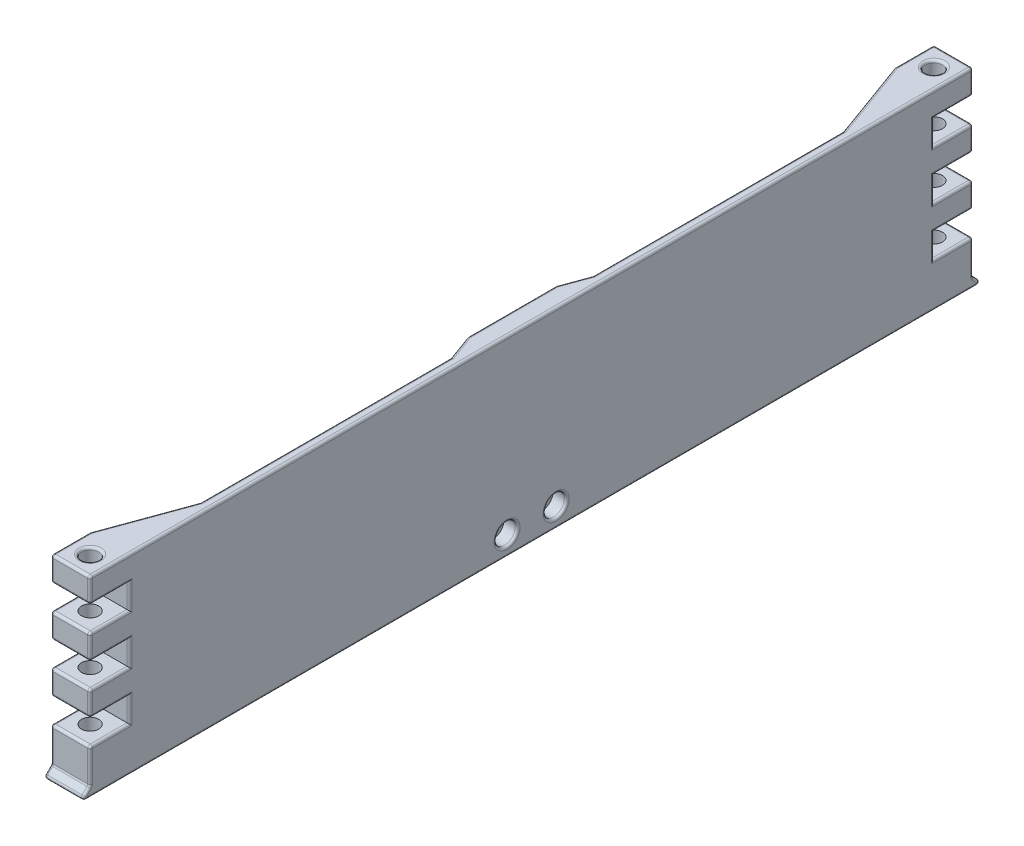
SolidWorks part; units mm, degrees
ref_plane "Front Plane" through (0, 0, 0) normal (0, 0, 1) x (1, 0, 0)
ref_plane "Top Plane" through (0, 0, 0) normal (0, 1, 0) x (1, 0, 0)
ref_plane "Right Plane" through (0, 0, 0) normal (1, 0, 0) x (0, 0, -1)
sketch "Sketch1" plane through (0, 0, 0) normal (1, 0, 0) x (0, 0, -1)
  line L1 (-45, -19.5) -> (45, -19.5)
  line L2 (-45, -5.5) -> (-45, -0.5)
  line L3 (-37, 19.5) -> (45, 19.5)
  line L4 (45, -19.5) -> (45, 19.5)
  line L5 (-45, -19.5) -> (45, 19.5) construction
  line L6 (-45, 19.5) -> (45, -19.5) construction
  line L8 (-47, -19.5) -> (-45, -19.5)
  line L12 (-37, 19.5) -> (-37, 14.5) construction
  line L13 (-37, 14.5) -> (-45, 14.5)
  line L14 (-37, 14.5) -> (-37, 9.5)
  line L15 (-37, 9.5) -> (-45, 9.5)
  line L16 (-37, 9.5) -> (-37, 4.5) construction
  line L17 (-37, 4.5) -> (-37, -0.5)
  line L18 (-37, -0.5) -> (-37, -5.5) construction
  line L19 (-37, -5.5) -> (-37, -10.5)
  line L20 (-37, 19.5) -> (-45, 19.5)
  line L21 (-45, 14.5) -> (-45, 19.5)
  line L22 (-37, -10.5) -> (-45, -10.5)
  line L23 (-37, -5.5) -> (-45, -5.5)
  line L24 (-37, -0.5) -> (-45, -0.5)
  line L25 (-37, 4.5) -> (-45, 4.5)
  line L26 (-45, 4.5) -> (-45, 9.5)
  line L43 (-45, -17.5) -> (-45, -10.5)
  line L44 (-45, -17.5) -> (-47, -19.5)
  line L45 (40, -19.5) -> (40, -15.5) construction
  line L46 (40, -15.5) -> (45, -15.5) construction
  circle A0 centre (40, -15.5) radius 2.15
  point P0 (0, 0)
  dimension "D9" = 4.3
  dimension "D1" = 39
  dimension "D2" = 90
  dimension "D3" = 2
  dimension "D4" = 8
  dimension "D5" = 5
  dimension "D6" = 2
  dimension "D7" = 4
  dimension "D8" = 5
extrude "Boss-Extrude1" add sketch "Sketch1" along normal blind 8 contours L13 L12 L3 L2 region at (0, -0.0156, -1.2577)
extrude "Boss-Extrude2" add sketch "Sketch1<3>" along normal blind 5.2 contours A0
sketch "Sketch1<3>" plane through (0, 0, 0) normal (1, 0, 0) x (0, 0, -1) same geometry as "Sketch1"
sketch "Sketch7" plane through (0, -19.5, 0) normal (0, -1, 0) x (1, 0, 0)
  line L1 (0, 47) -> (0, -45) construction
  line L2 (4, 41) -> (4, 45) construction
  line L4 (8, 37) -> (0, 37) construction
  line L5 (0, 37) -> (0, 45) construction
  line L6 (4, 45) -> (4, 47) construction
  line L7 (4, 45) -> (7, 45) construction
  line L8 (8, 37) -> (0, 45) construction
  line L9 (8, 47) -> (0, 47) construction
  line L10 (1.175, 39.369) -> (4, 37.738)
  line L11 (4, 37.738) -> (6.825, 39.369)
  line L12 (6.825, 39.369) -> (6.825, 42.631)
  line L13 (6.825, 42.631) -> (4, 44.262)
  line L14 (4, 44.262) -> (1.175, 42.631)
  line L15 (1.175, 42.631) -> (1.175, 39.369)
  line L16 (4, 37.738) -> (4, 37) construction
  line L17 (0, 45) -> (8, 45)
  line L18 (8, 47) -> (8, -45) construction
  line L19 (0, 45) -> (0, 47)
  circle A0 centre (4, 41) radius 1.75
  circle A1 centre (4, 41) radius 2.825 construction
  point P1 (0, 0)
  point P26 (4, 41)
  dimension "D4" = 5.65
  dimension "D5" = 3.5
  dimension "D1" = 2
  dimension "D3" = 8
  dimension "D6" = 2
extrude "Cut-Extrude3" cut sketch "Sketch7" against normal through all both and the other way through all contours A0 region at (4, -19.5, 41)
extrude "Cut-Extrude4" cut sketch "Sketch7<3>" against normal blind 6 and the other way through all contours L14 L15 L10 L11 L12 L13 A0 region at (1.2613, -19.5, 41)
sketch "Sketch7<3>" plane through (0, -19.5, 0) normal (0, -1, 0) x (1, 0, 0) same geometry as "Sketch7"
sketch "Sketch8" plane through (0, 19.5, 0) normal (0, 1, 0) x (1, 0, 0)
  line L0 (0, -37) -> (6, -20.5151)
  line L1 (0, -45) -> (0, 45) construction
  line L4 (0, -37) -> (0, 45)
  line L11 (6, -20.5151) -> (6, 30.505)
  line L12 (8, -45) -> (8, 45) construction
  line L13 (6, 30.505) -> (4, 36)
  line L16 (8, -45) -> (8, 45)
  line L17 (8, 45) -> (4, 45)
  line L18 (8, 45) -> (0, 45) construction
  line L19 (4, 45) -> (0, 45)
  line L20 (4, 45) -> (4, 36)
  line M4 (0, 45) -> (0, -45)
  line M7 (8, 45) -> (0, 45)
  dimension "D1" = 200
  dimension "D2" = 8
  dimension "D3" = 2
  dimension "D4" = 160
  dimension "D5" = 9
extrude "Cut-Extrude5" cut sketch "Sketch8" against normal through all contours L20 L0 L11 L13 M7 M4 region at (2.7655, 19.5, -6.2267)
mirror "Mirror2" about plane through (8, 0, -45) normal (0, 0, 1) of bodies 111 109
fillet "Fillet1" radius 0.5 92 edges at (3, -19.5, 28.7576) (3, -19.5, -118.7576) (0, -18.5, -136) (0, -18.5, 46) (4, -17.5, -135) (4, -10.5, -135) (0, -14, -135) (4, -5.5, -135) (4, -0.5, -135) (0, -3, -135) (4, 4.5, -135) (4, 9.5, -135) (0, 7, -135) (4, 14.5, -135) (0, 17, -135) (8, -10.5, 41) (8, -8, 37) (8, -5.5, 41) (8, -0.5, 41) (8, 2, 37) (8, 4.5, 41) (8, 9.5, 41) (8, 12, 37) (8, 14.5, 41) (8, 17, -135) (8, 14.5, -131) (8, 12, -127) (8, 9.5, -131) (8, 7, -135) (8, 4.5, -131) (8, 2, -127) (8, -0.5, -131) (8, -3, -135) (8, -5.5, -131) (8, -8, -127) (8, -10.5, -131) (8, -14, -135) (8, -18.5, -136) (8, -19.5, -45) (8, -18.5, 46) (4, -10.5, 45) (8, -14, 45) (4, -17.5, 45) (0, -14, 45) (4, -0.5, 45) (8, -3, 45) (4, -5.5, 45) (0, -3, 45) (4, 9.5, 45) (8, 7, 45) (4, 4.5, 45) (0, 7, 45) (8, 17, 45) (4, 14.5, 45) (0, 17, 45) (4, 19.5, -129.25) (4, 19.5, 39.25) (3, 19.5, -118.7576) (0, 19.5, -131) (4, 19.5, -135) (8, 19.5, -45) (4, 19.5, 45) (0, 19.5, 41) (3, 19.5, 28.7576) (0, -19.5, 42) (0, -19.5, -132) (0, 14.5, 41) (0, 9.5, 41) (0, 4.5, 41) (0, -0.5, 41) (0, -5.5, 41) (0, -10.5, 41) (0, -10.5, -131) (0, -5.5, -131) (0, -0.5, -131) (0, 4.5, -131) (0, 9.5, -131) (0, 14.5, -131) (4, -19.5, 47) (4, -19.5, -137) (8, -15.5, -47.85) (8, -15.5, -42.15) (6, 19.5, -4.995) (5, 19.5, -33.2525) (4, 19.5, -45) (5, 19.5, -56.7475) (6, 19.5, -85.005) (6, -19.5, -85.005) (5, -19.5, -56.7475) (4, -19.5, -45) (5, -19.5, -33.2525) (6, -19.5, -4.995)
